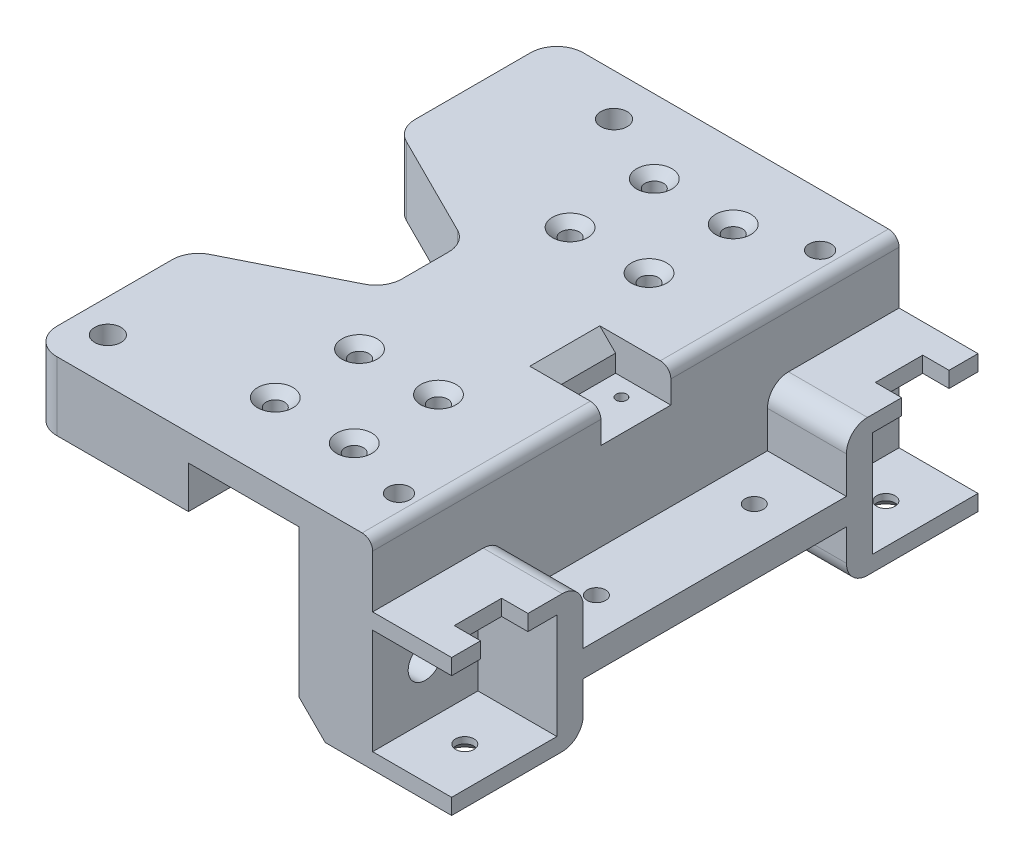
SolidWorks part; units mm, degrees
ref_plane "Front Plane" through (0, 0, 0) normal (0, 0, 1) x (1, 0, 0)
ref_plane "Top Plane" through (0, 0, 0) normal (0, 1, 0) x (1, 0, 0)
ref_plane "Right Plane" through (0, 0, 0) normal (1, 0, 0) x (0, 0, -1)
sketch "Sketch1" plane through (0, 0, 0) normal (0, 1, 0) x (1, 0, 0)
  line L0 (0, 50) -> (0, -50) construction
  line L1 (-10, 50) -> (10, 50)
  line L2 (-10, 50) -> (-10, -50)
  line L3 (-10, -50) -> (10, -50)
  line L4 (10, 50) -> (10, -50) construction
  line L5 (-10, 50) -> (10, -50) construction
  line L6 (-10, -50) -> (10, 50) construction
  line L7 (-7.5, 36) -> (7.5, 36) construction
  line L8 (-7.5, 36) -> (7.5, 20) construction
  line L9 (-10, 0) -> (10, 0) construction
  line L10 (-7.5, -36) -> (7.5, -20) construction
  line L11 (-7.5, -36) -> (7.5, -36) construction
  line L12 (-7.5, 20) -> (7.5, 20) construction
  line L13 (10, 50) -> (11, 50)
  line L14 (11, 50) -> (11, -50)
  line L15 (11, -50) -> (10, -50)
  circle A0 centre (-7.5, 36) radius 1.75
  circle A1 centre (7.5, 36) radius 1.75
  circle A2 centre (-7.5, 20) radius 1.75
  circle A3 centre (7.5, 20) radius 1.75
  circle A4 centre (7.5, -20) radius 1.75
  circle A5 centre (-7.5, -20) radius 1.75
  circle A6 centre (7.5, -36) radius 1.75
  circle A7 centre (-7.5, -36) radius 1.75
  point P0 (0, 0)
  point P16 (0, 36)
  dimension "D2" = 3.5
  dimension "D1" = 20
  dimension "D3" = 15
  dimension "D4" = 16
  dimension "D5" = 100
  dimension "D6" = 20
  dimension "D7" = 1
extrude "Boss-Extrude1" add sketch "Sketch1" along normal blind 5
sketch "Sketch2" plane through (11, 0, 0) normal (1, 0, 0) x (0, 0, -1)
  line L1 (-50, 5) -> (50, 5)
  line L2 (-50, 5) -> (-50, -33)
  line L3 (-50, -33) -> (50, -33)
  line L5 (50, 5) -> (50, -33)
  line L6 (50, 5) -> (50, 0) construction
  line L7 (-50, 5) -> (-50, 0) construction
  line L8 (-50, 5) -> (50, 5) construction
  dimension "D1" = 38
extrude "Boss-Extrude2" add sketch "Sketch2" along normal blind 14
sketch "Sketch3" plane through (25, 0, 0) normal (1, 0, 0) x (0, 0, -1)
  line L0 (0, 5) -> (0, -33) construction
  line L1 (-25, -18) -> (25, -18)
  line L2 (-25, -18) -> (-25, -23)
  line L3 (-25, -23) -> (25, -23)
  line L4 (25, -18) -> (25, -23)
  line L5 (50, 5) -> (-50, 5) construction
  line L6 (-50, -33) -> (50, -33) construction
  point P10 (0, -18)
  dimension "D1" = 5
  dimension "D2" = 50
  dimension "D3" = 10
extrude "Boss-Extrude3" add sketch "Sketch3" along normal blind 15
sketch "Sketch4" plane through (0, -18, 0) normal (0, 1, 0) x (1, 0, 0)
  line L0 (25, 0) -> (40, 0) construction
  line L1 (25, 25) -> (25, -25) construction
  line L2 (40, 25) -> (40, -25) construction
  line L3 (32.5, -15) -> (32.5, 15) construction
  circle A0 centre (32.5, 15) radius 1.75
  circle A1 centre (32.5, -15) radius 1.75
  point P8 (32.5, 0)
  dimension "D1" = 30
  dimension "D2" = 3.5
extrude "Cut-Extrude1" cut sketch "Sketch4" against normal through all
sketch "Sketch8" plane through (25, 0, 0) normal (1, 0, 0) x (0, 0, -1)
  line L0 (-50, 5) -> (-50, -33) construction
  line L1 (-50, -7) -> (-25, -7)
  line L2 (-50, -7) -> (-50, -10)
  line L3 (-50, -33) -> (-25, -33)
  line L4 (-25, -7) -> (-25, -33)
  line L5 (-50, -30) -> (-50, -33)
  line L6 (-50, -30) -> (-30, -30)
  line L8 (-50, -10) -> (-30, -10)
  line L9 (-30, -30) -> (-30, -10)
  line L10 (0, 20.9) -> (0, -20.9) construction
  line L11 (30, -30) -> (30, -10)
  line L12 (50, -10) -> (30, -10)
  line L13 (50, -30) -> (30, -30)
  line L14 (50, -30) -> (50, -33)
  line L15 (25, -7) -> (25, -33)
  line L16 (50, -33) -> (25, -33)
  line L17 (50, -7) -> (50, -10)
  line L18 (50, -7) -> (25, -7)
  line L19 (-50, -33) -> (50, -33) construction
  dimension "D1" = 3
  dimension "D2" = 5
  dimension "D3" = 3
  dimension "D4" = 20
  dimension "D5" = 20
extrude "Boss-Extrude6" add sketch "Sketch8" along normal blind 15
sketch "Sketch9" plane through (25, 0, 0) normal (1, 0, 0) x (0, 0, -1)
  line L0 (-50, -10) -> (-30, -30) construction
  line L1 (50, -10) -> (30, -30) construction
  circle A0 centre (-40, -20) radius 3.25
  circle A1 centre (40, -20) radius 3.25
  dimension "D1" = 6.5
extrude "Cut-Extrude3" cut sketch "Sketch9" against normal through all
sketch "Sketch10" plane through (11, 0, 0) normal (-1, 0, 0) x (0, 0, 1)
  circle A0 centre (-40, -20) radius 5.25
  circle A1 centre (40, -20) radius 5.25
  dimension "D1" = 10.5
extrude "Cut-Extrude4" cut sketch "Sketch10" against normal offset from surface (9 mm away) 5 up to face at (25, -20, 36.75)
sketch "Sketch11" plane through (0, -7, 0) normal (0, 1, 0) x (1, 0, 0)
  line L0 (40, -25) -> (40, -50) construction
  line L1 (40, -35.5) -> (35, -35.5)
  line L2 (40, -35.5) -> (40, -44.5)
  line L3 (40, -44.5) -> (35, -44.5)
  line L4 (35, -35.5) -> (35, -44.5)
  line L5 (35, -40) -> (40, -40) construction
  line L6 (40, -50) -> (25, -50) construction
  line L7 (-10, 0) -> (40, 0) construction
  line L8 (-10, 50) -> (-10, -50) construction
  line L9 (40, 25) -> (40, -25) construction
  line L10 (40, -35.5) -> (35, -35.5)
  line L11 (40, -44.5) -> (35, -44.5)
  line L12 (35, 40) -> (40, 40) construction
  line L13 (40, 44.5) -> (35, 44.5)
  line L14 (40, 35.5) -> (35, 35.5)
  line L15 (35, 35.5) -> (35, 44.5)
  line L16 (40, 44.5) -> (35, 44.5)
  line L17 (40, 35.5) -> (40, 44.5)
  line L18 (40, 35.5) -> (35, 35.5)
  line M7 (40, -50) -> (40, -25)
  dimension "D1" = 9
  dimension "D2" = 10
  dimension "D3" = 5
extrude "Cut-Extrude5" cut sketch "Sketch11" against normal up to next contours L1 L4 L3 M7 | L14 L17 L13 L15 region at (37.5, -7, 40) region at (37.5, -7, -40)
sketch "Sketch12" plane through (0, -30, 0) normal (0, 1, 0) x (1, 0, 0)
  line L0 (40, -40) -> (25, -40) construction
  line L1 (40, -30) -> (40, -50) construction
  line L2 (25, -25) -> (25, -50) construction
  line L3 (-20.9, 0) -> (20.9, 0) construction
  circle A0 centre (32.5, -40) radius 1.75
  circle A2 centre (32.5, 40) radius 1.75
  dimension "D1" = 3.5
extrude "Cut-Extrude6" cut sketch "Sketch12" against normal through all
sketch "Sketch13" plane through (-10, 0, 0) normal (-1, 0, 0) x (0, 0, 1)
  line L1 (-50, 5) -> (50, 5)
  line L2 (-50, 5) -> (-50, -8)
  line L3 (-50, -8) -> (50, -8)
  line L4 (50, 5) -> (50, -8)
  dimension "D1" = 13
extrude "Boss-Extrude7" add sketch "Sketch13" along normal blind 30
sketch "Sketch14" plane through (0, 5, 0) normal (0, 1, 0) x (1, 0, 0)
  line L6 (-27.65, 42) -> (-27.65, -41.58) construction
  line L12 (-21.15, 35.5) -> (40, 35.5) construction
  line L18 (-33.73, -35.5) -> (40, -35.5) construction
  circle A0 centre (-21.15, 42) radius 2.5
  circle A1 centre (-33.73, -41.58) radius 2.5
  circle A2 centre (-33.73, -41.58) radius 6.08 construction
  circle A3 centre (-21.15, 42) radius 6.5 construction
  dimension "D1" = 5
  dimension "D2" = 5
  dimension "D4" = 12.16
  dimension "D5" = 13
  dimension "D3" = 21.15
extrude "Cut-Extrude7" cut sketch "Sketch14" against normal through all
sketch "Sketch15" plane through (0, -8, 0) normal (0, -1, 0) x (1, 0, 0)
  line L0 (-40, -50) -> (-40, 50) construction
  line L1 (-29.63, 43.9471) -> (-33.73, 46.3143)
  line L2 (-33.73, 46.3143) -> (-37.83, 43.9471)
  line L3 (-37.83, 43.9471) -> (-37.83, 39.2129)
  line L4 (-37.83, 39.2129) -> (-33.73, 36.8457)
  line L5 (-33.73, 36.8457) -> (-29.63, 39.2129)
  line L6 (-29.63, 39.2129) -> (-29.63, 43.9471)
  line L7 (-17.05, -44.3671) -> (-17.05, -39.6329)
  line L8 (-17.05, -39.6329) -> (-21.15, -37.2657)
  line L9 (-21.15, -37.2657) -> (-25.25, -39.6329)
  line L10 (-25.25, -39.6329) -> (-25.25, -44.3671)
  line L11 (-25.25, -44.3671) -> (-21.15, -46.7343)
  line L12 (-21.15, -46.7343) -> (-17.05, -44.3671)
  circle A0 centre (-33.73, 41.58) radius 4.1 construction
  circle A1 centre (-21.15, -42) radius 4.1 construction
  dimension "D1" = 8.2
extrude "Cut-Extrude8" cut sketch "Sketch15" against normal blind 5
sketch "Sketch16" plane through (0, 5, 0) normal (0, 1, 0) x (1, 0, 0)
  line L0 (20, 40) -> (40, 40) construction
  line L1 (40, 40) -> (40, -40) construction
  line L2 (40, -40) -> (20, -40) construction
  line L3 (20, -40) -> (20, 40) construction
  line L4 (40, 50) -> (40, 30) construction
  line L5 (40, -30) -> (40, -50) construction
  circle A0 centre (20, 40) radius 2.1
  circle A1 centre (20, -40) radius 2.1
  dimension "D1" = 4.2
  dimension "D2" = 4.2
  dimension "D3" = 20
extrude "Cut-Extrude9" cut sketch "Sketch16" against normal blind 4
chamfer "Chamfer1" distance 1.6 angle 45 8 edges at (7.5, 5, 34.25) (-7.5, 5, 34.25) (7.5, 5, 18.25) (-7.5, 5, 18.25) (7.5, 5, -18.25) (-7.5, 5, -18.25) (7.5, 5, -34.25) (-7.5, 5, -34.25)
sketch "Sketch17" plane through (0, 5, 0) normal (0, 1, 0) x (1, 0, 0)
  line L0 (-40, 20) -> (-15, 7.5)
  line L1 (-40, -50) -> (-40, 50) construction
  line L2 (-15, 7.5) -> (-15, -7.5)
  line L3 (-15, -7.5) -> (-40, -20)
  line L4 (-40, -20) -> (-40, 20)
  point P5 (-15, 0)
  dimension "D1" = 15
  dimension "D2" = 25
  dimension "D3" = 40
extrude "Cut-Extrude10" cut sketch "Sketch17" against normal through all
chamfer "Chamfer2" distance 1.8 angle 45 2 edges at (32.5, -33, -41.75) (32.5, -33, 41.75)
chamfer "Chamfer3" distance 5 angle 45 1 edges at (11, -33, 0)
sketch "Sketch18" plane through (0, 1, 0) normal (0, 1, 0) x (1, 0, 0)
  circle A0 centre (20, 40) radius 1.75
  circle A1 centre (20, -40) radius 1.75
  dimension "D1" = 3.5
  dimension "D2" = 3.5
extrude "Cut-Extrude11" cut sketch "Sketch18" against normal blind 4
fillet "Fillet1" radius 5 6 edges at (-40, -1.5, 50) (-40, -1.5, 20) (-15, -1.5, 7.5) (-15, -1.5, -7.5) (-40, -1.5, -20) (-40, -1.5, -50)
fillet "Fillet2" radius 4 4 edges at (32.5, -33, -25) (32.5, -7, -25) (32.5, -33, 25) (32.5, -7, 25)
sketch "Sketch19" plane through (25, 0, 0) normal (1, 0, 0) x (0, 0, -1)
  line L0 (50, 5) -> (-50, 5) construction
  line L1 (-6.65, 5) -> (6.65, 5)
  line L2 (-6.65, 5) -> (-6.65, -1.3)
  line L3 (-6.65, -1.3) -> (6.65, -1.3)
  line L4 (6.65, 5) -> (6.65, -1.3)
  point P4 (-8.882, 5)
  point P5 (0, 0)
  point P7 (0, 5)
  dimension "D1" = 13.3
  dimension "D2" = 6.3
extrude "Cut-Extrude12" cut sketch "Sketch19" against normal blind 10.5
sketch "Sketch20" plane through (0, -1.3, 0) normal (0, 1, 0) x (1, 0, 0)
  line L0 (19, 3.25) -> (19, -3.25) construction
  line L3 (14.5, 6.65) -> (14.5, -6.65) construction
  line L4 (18, 3.25) -> (18, -3.25) construction
  circle A0 centre (19, 3.25) radius 1
  circle A1 centre (19, -3.25) radius 1
  point P2 (14.5, 0)
  point P3 (19, 0)
  dimension "D1" = 2
  dimension "D2" = 6.5
  dimension "D3" = 3.5
extrude "Cut-Extrude13" cut sketch "Sketch20" against normal blind 3
chamfer "Chamfer4" distance 3 angle 45 1 edges at (14.5, 5, 0)
fillet "Fillet3" radius 2 2 edges at (25, 5, -28.325) (25, 5, 28.325)
